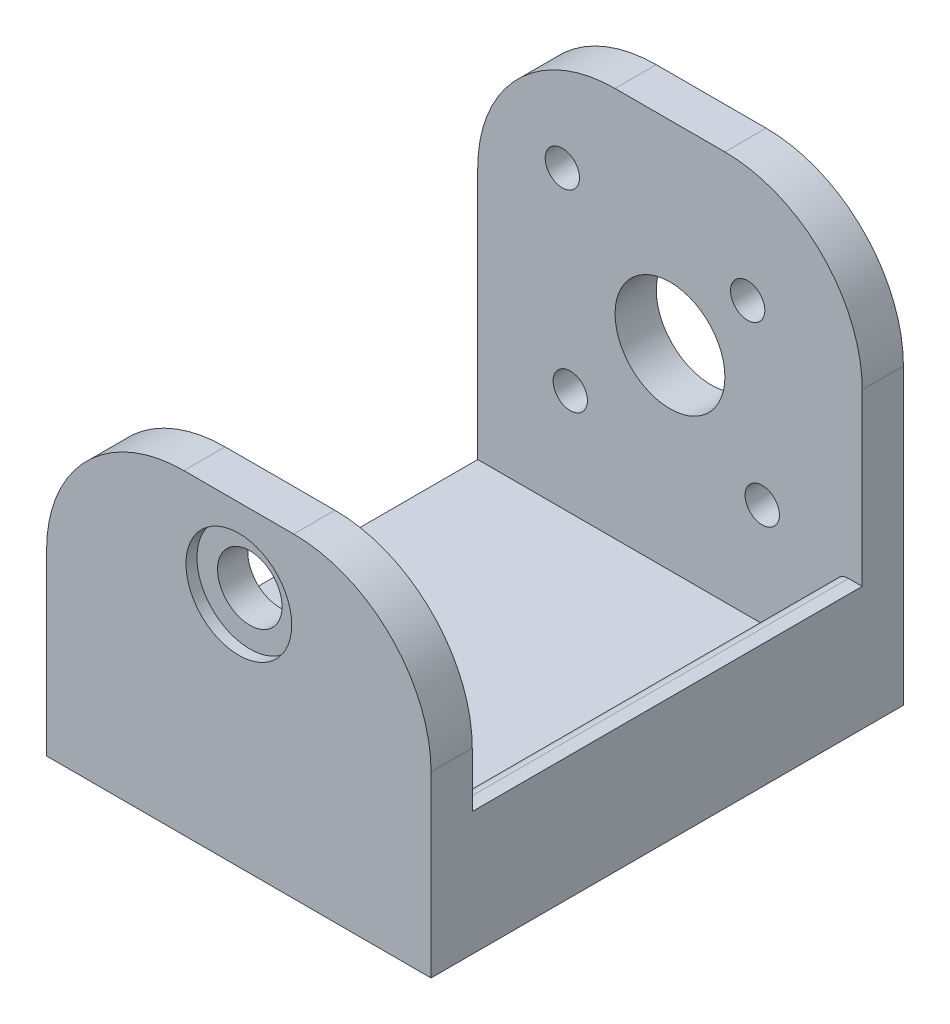
SolidWorks part; units mm, degrees
ref_plane "Front Plane" through (0, 0, 0) normal (0, 0, 1) x (1, 0, 0)
ref_plane "Top Plane" through (0, 0, 0) normal (0, 1, 0) x (1, 0, 0)
ref_plane "Right Plane" through (0, 0, 0) normal (1, 0, 0) x (0, 0, -1)
sketch "Sketch1" plane through (0, 0, 0) normal (1, 0, 0) x (0, 0, -1)
  line L0 (-14.2, 20) -> (-14.2, 0)
  line L1 (-14.2, 0) -> (14.2, 0)
  line L2 (14.2, 0) -> (14.2, 28.4)
  point P3 (0, 0)
  dimension "D1" = 28.4
  dimension "D2" = 28.4
  dimension "D3" = 20
extrude "Extrude-Thin1" add sketch "Sketch1" along normal mid plane 28 thin thin type one direction wall 3
sketch "Sketch3" plane through (0, 0, -14.2) normal (0, 0, 1) x (1, 0, 0)
  line L0 (-6.7175, 20.9175) -> (6.7175, 7.4825) construction
  line L1 (-5.6569, 8.5431) -> (5.6569, 19.8569) construction
  line L2 (0, -1000) -> (0, 49000) construction
  line L3 (14, 0) -> (-14, 0) construction
  line L4 (14, 0) -> (14, 28.4) construction
  circle A0 centre (0, 14.2) radius 14 construction
  point P4 (0, 14.2)
  point P5 (0, 14.2)
  point P7 (0, 0)
  point P11 (0, 0)
  point P14 (14, 14.2)
  point P15 (0, 0)
  dimension "D4" = 28
  dimension "D1" = 19
  dimension "D2" = 16
  dimension "D3" = 45
hole_wizard "M3x0.5 Tapped Hole1" positions "Sketch4" profile "Sketch5" tap size "M3x0.5" standard "ANSI Metric" end condition up to next
sketch "Sketch4" plane through (0, 0, -17.2) normal (0, 0, -1) x (-1, 0, 0)
  point P0 (-5.6569, 19.8569)
  point P2 (7.8394, 21.4652)
  point P4 (7.2628, 7.7015)
  point P6 (-6.7175, 7.4825)
  point P9 (0, 0)
  point P11 (0, 0)
sketch "Sketch5" plane through (5.6569, 19.8569, -17.2) normal (1, 0, 0) x (0, 1, 0)
  line L0 (0, 0) -> (0, 3)
  line L1 (0, 3) -> (1.25, 3)
  line L2 (1.25, 3) -> (1.25, 0)
  line L5 (1.25, 0) -> (0, 0)
  line L11 (0, -6.35) -> (0, 107.95) construction
  dimension "Thru Tap Drill Dia." = 2.5
  dimension "Thru Tap Drill Depth" = 3
cosmetic thread "Hole Thread1" parameters "D2"=3
cosmetic thread "Hole Thread2" parameters "D2"=3
cosmetic thread "Hole Thread3" parameters "D2"=3
cosmetic thread "Hole Thread4" parameters "D2"=3
sketch "Sketch7" plane through (0, 0, 17.2) normal (0, 0, 1) x (1, 0, 0)
  circle A0 centre (0, 14.2) radius 3.85
  point P2 (0, 0)
  dimension "D1" = 7.7
extrude "Cut-Extrude1" cut sketch "Sketch7" against normal blind 0.8
sketch "Sketch8" plane through (0, 0, 16.4) normal (0, 0, 1) x (1, 0, 0)
  circle A0 centre (0, 14.2) radius 2.35
  dimension "D1" = 4.7
extrude "Cut-Extrude2" cut sketch "Sketch8" against normal up to next
sketch "Sketch9" plane through (0, 0, -17.2) normal (0, 0, -1) x (-1, 0, 0)
  circle A0 centre (0, 14.2) radius 4
  point P2 (0, 0)
  dimension "D1" = 8
extrude "Cut-Extrude3" cut sketch "Sketch9" against normal up to next contours A0
fillet "Fillet1" radius 10 4 edges at (-14, 28.4, -15.7) (14, 28.4, -15.7) (-14, 20, 15.7) (14, 20, 15.7)
sketch "Sketch10" plane through (14, 0, 0) normal (1, 0, 0) x (0, 0, -1)
  line L0 (14.2, 6) -> (-14.2, 6)
  line L1 (14.2, 0) -> (14.2, 18.4) construction
  line L2 (-14.2, 10) -> (-14.2, 0) construction
  line L6 (-14.2, 0) -> (14.2, 0) construction
  dimension "D1" = 6
rib "Rib7" sketch "Sketch10" sketch "Sketch10" thickness 2 extrusion direction parallel to sketch draft on no parameters "D1"=2
fillet "Fillet2" radius 1 1 edges at (12, 6, 0)
fillet "Fillet3" radius 4 1 edges at (12, 0, 0)
